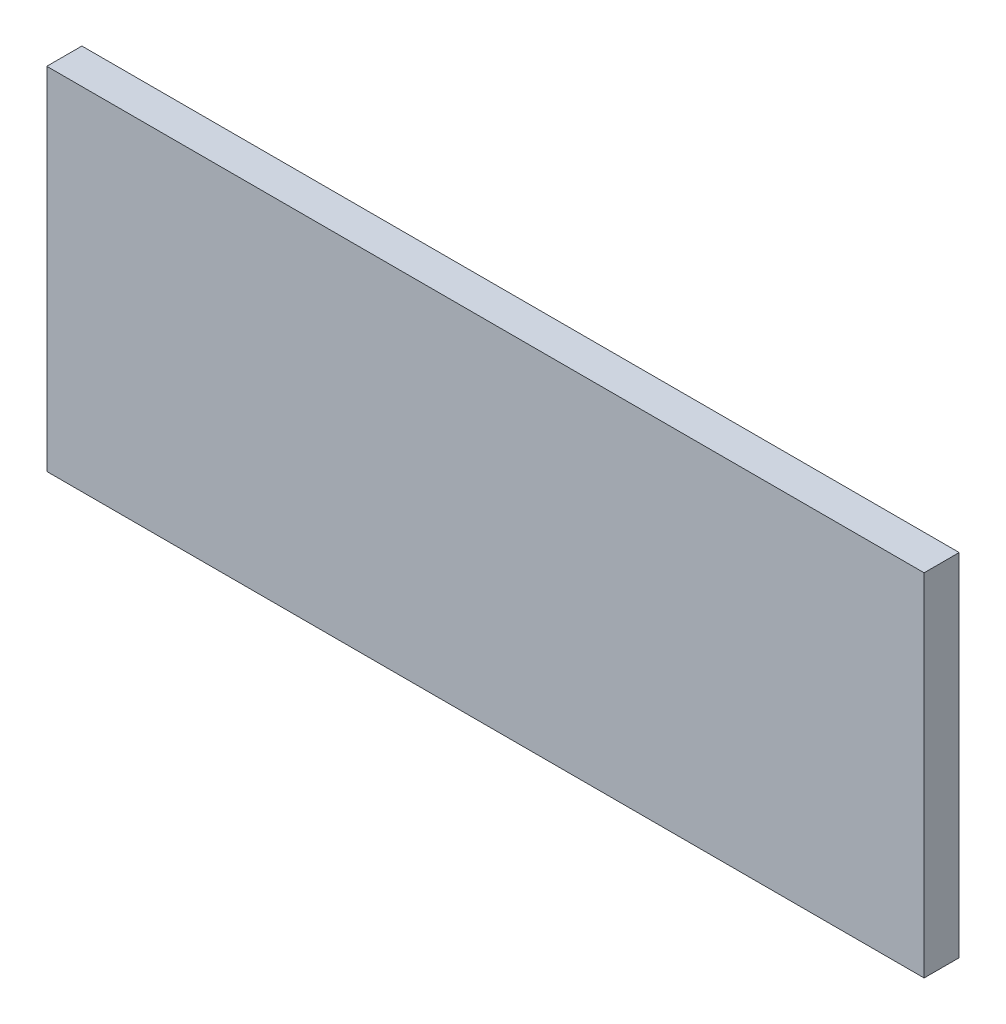
SolidWorks part; units mm, degrees
material "Лист 4,0 ГОСТ 19903-2015 / Ст3сп ГОСТ 14637-89"
ref_plane "Спереди" through (0, 0, 0) normal (0, 0, 1) x (1, 0, 0)
ref_plane "Сверху" through (0, 0, 0) normal (0, 1, 0) x (1, 0, 0)
ref_plane "Справа" through (0, 0, 0) normal (1, 0, 0) x (0, 0, -1)
sketch "Эскиз1" plane through (0, 0, 0) normal (0, 0, 1) x (1, 0, 0)
  line L1 (-50, -20) -> (50, -20)
  line L2 (-50, -20) -> (-50, 20)
  line L3 (-50, 20) -> (50, 20)
  line L4 (50, -20) -> (50, 20)
extrude "Бобышка-Вытянуть1" add sketch "Эскиз1" along normal blind 4
sketch "Эскиз2" plane through (0, 0, 0) normal (0, 0, 1) x (1, 0, 0)
  line L1 (50, -20) -> (100, -20)
  line L2 (50, -20) -> (50, 20)
  line L3 (50, 20) -> (100, 20)
  line L4 (100, -20) -> (100, 20)
extrude "Бобышка-Вытянуть2" [suppressed] add sketch "Эскиз2" along normal blind 4
sketch "Эскиз3" plane through (0, 0, 0) normal (0, 0, 1) x (1, 0, 0)
  line L1 (100, -20) -> (150, -20)
  line L2 (100, -20) -> (100, 20)
  line L3 (100, 20) -> (150, 20)
  line L4 (150, -20) -> (150, 20)
extrude "Бобышка-Вытянуть3" [suppressed] add sketch "Эскиз3" along normal blind 4
